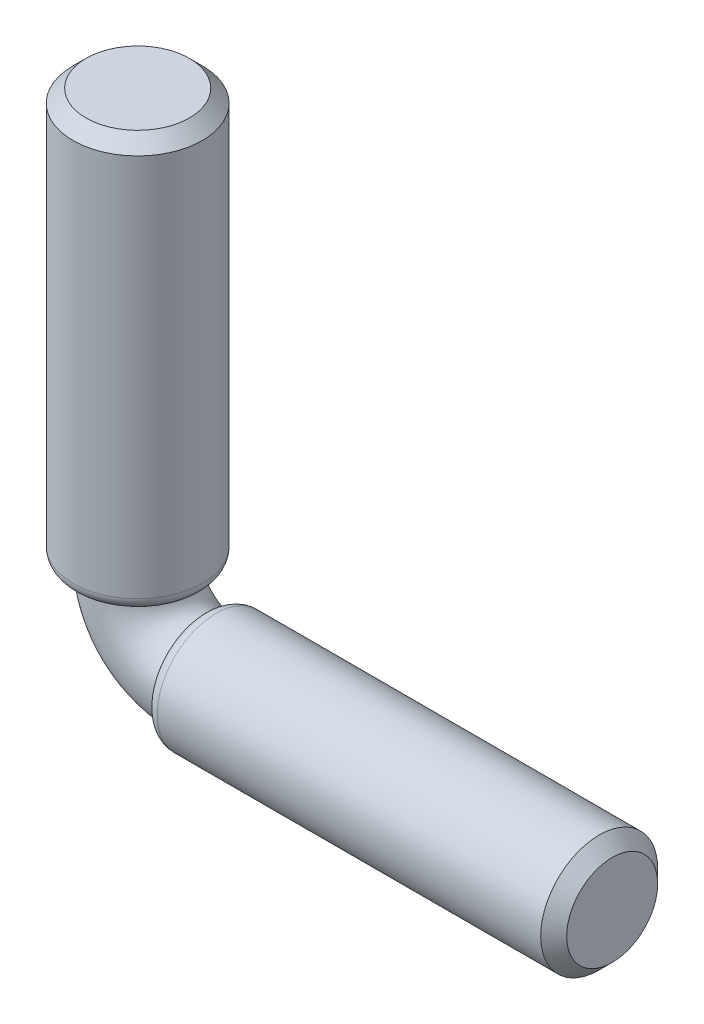
SolidWorks part; units mm, degrees
ref_plane "Front Plane" through (0, 0, 0) normal (0, 0, 1) x (1, 0, 0)
ref_plane "Top Plane" through (0, 0, 0) normal (0, 1, 0) x (1, 0, 0)
ref_plane "Right Plane" through (0, 0, 0) normal (1, 0, 0) x (0, 0, -1)
sketch "Sketch1" plane through (0, 0, 0) normal (0, 0, 1) x (1, 0, 0)
  line L0 (0, 31.5) -> (0, 0)
  line L1 (5, -5) -> (36.5, -5)
  arc A0 (0, 0) -> (5, -5) centre (5, 0) ccw
  dimension "D1" = 5
  dimension "D2" = 31.5
  dimension "D3" = 31.5
sweep "Sweep1" add path "Sketch1" circular profile diameter 7 parameters "D3"=7
sketch "Sketch10" plane through (0, 31.5, 0) normal (0, 1, 0) x (1, 0, 0)
  circle A0 centre (0, 0) radius 4.9755
  dimension "D1" = 9.9511
extrude "Boss-Extrude1" add sketch "Sketch10" against normal blind 31.5 contours A0
sketch "Sketch11" plane through (36.5, 0, 0) normal (1, 0, 0) x (0, 0, -1)
  circle A0 centre (0, -5) radius 4.5
  dimension "D1" = 9
extrude "Boss-Extrude2" add sketch "Sketch11" against normal blind 31.5
chamfer "Chamfer1" distance 1 1 edges at (-4.9755, 31.5, 0)
chamfer "Chamfer2" distance 1 angle 45 1 edges at (36.5, -5, -4.5)
fillet "Fillet3" radius 1 2 edges at (5, -5, -4.5) (-4.9755, 0, 0)
